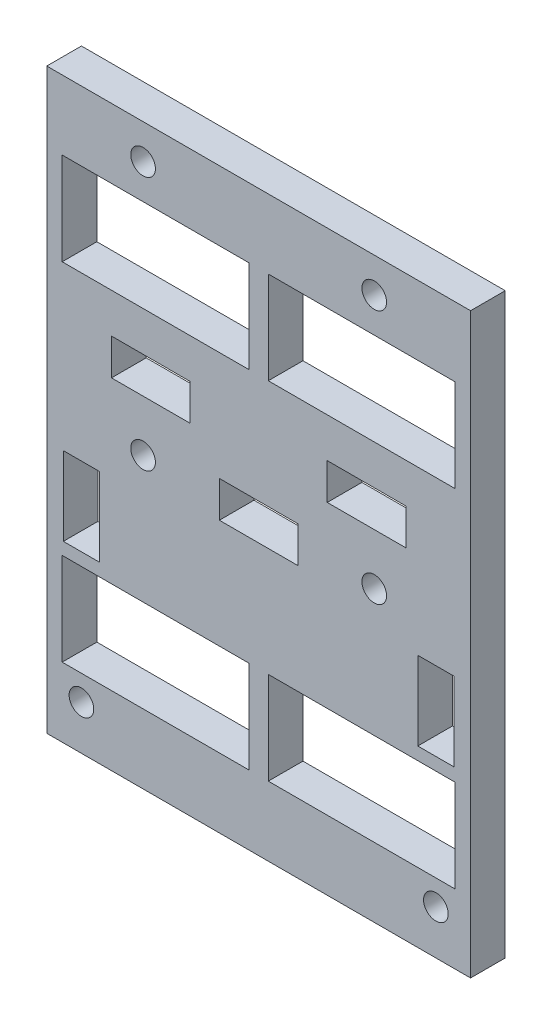
SolidWorks part; units mm, degrees
ref_plane "Front Plane" through (0, 0, 0) normal (0, 0, 1) x (1, 0, 0)
ref_plane "Top Plane" through (0, 0, 0) normal (0, 1, 0) x (1, 0, 0)
ref_plane "Right Plane" through (0, 0, 0) normal (1, 0, 0) x (0, 0, -1)
sketch "Sketch1" plane through (0, 0, 0) normal (0, 0, 1) x (1, 0, 0)
  line L0 (0, -37.5) -> (0, 37.5) construction
  line L1 (-27.5, -37.5) -> (27.5, -37.5)
  line L2 (-27.5, -37.5) -> (-27.5, 37.5)
  line L3 (-27.5, 37.5) -> (27.5, 37.5)
  line L4 (27.5, -37.5) -> (27.5, 37.5)
  line L5 (-27.5, -37.5) -> (27.5, 37.5) construction
  line L6 (-27.5, 37.5) -> (27.5, -37.5) construction
  line L7 (-27.5, 0) -> (27.5, 0) construction
  line L8 (-27.5, 22.5) -> (27.5, 22.5) construction
  line L9 (25.5, 16.5) -> (1.25, 28.5) construction
  line L10 (-25.5, 28.5) -> (-1.25, 28.5)
  line L11 (-25.5, 28.5) -> (-25.5, 16.5)
  line L12 (-25.5, 16.5) -> (-1.25, 16.5)
  line L13 (-1.25, 28.5) -> (-1.25, 16.5)
  line L14 (-25.5, 28.5) -> (-1.25, 16.5) construction
  line L15 (-25.5, 16.5) -> (-1.25, 28.5) construction
  line L16 (25.5, 28.5) -> (1.25, 16.5) construction
  line L17 (1.25, 28.5) -> (1.25, 16.5)
  line L18 (25.5, 16.5) -> (1.25, 16.5)
  line L19 (25.5, 28.5) -> (25.5, 16.5)
  line L20 (25.5, 28.5) -> (1.25, 28.5)
  line L21 (25.5, -28.5) -> (1.25, -16.5) construction
  line L22 (-25.5, -16.5) -> (-1.25, -28.5) construction
  line L23 (-25.5, -28.5) -> (-1.25, -16.5) construction
  line L24 (25.5, -16.5) -> (1.25, -28.5) construction
  line L25 (25.5, -28.5) -> (1.25, -28.5)
  line L26 (25.5, -28.5) -> (25.5, -16.5)
  line L27 (25.5, -16.5) -> (1.25, -16.5)
  line L28 (1.25, -28.5) -> (1.25, -16.5)
  line L29 (-1.25, -28.5) -> (-1.25, -16.5)
  line L30 (-25.5, -16.5) -> (-1.25, -16.5)
  line L31 (-25.5, -28.5) -> (-25.5, -16.5)
  line L32 (-25.5, -28.5) -> (-1.25, -28.5)
  point P0 (0, 0)
  point P12 (-13.375, 22.5)
  point P21 (13.375, 22.5)
  point P30 (13.375, -22.5)
  point P31 (-13.375, -22.5)
  dimension "D1" = 55
  dimension "D2" = 75
  dimension "D3" = 22.5
  dimension "D4" = 24.25
  dimension "D5" = 12
  dimension "D6" = 1.25
extrude "Boss-Extrude1" add sketch "Sketch1" along normal blind 4.5
sketch "Sketch2" plane through (0, 0, 4.5) normal (0, 0, 1) x (1, 0, 0)
  line L0 (0, -37.5) -> (0, 37.5) construction
  line L1 (-27.5, -37.5) -> (27.5, -37.5) construction
  line L2 (27.5, 37.5) -> (-27.5, 37.5) construction
  line L3 (-27.5, 0) -> (27.5, 0) construction
  line L4 (-27.5, 37.5) -> (-27.5, -37.5) construction
  line L5 (27.5, -37.5) -> (27.5, 37.5) construction
  line L6 (-15, 0) -> (15, 0) construction
  circle A0 centre (-15, 33) radius 1.6
  circle A1 centre (15, 33) radius 1.6
  circle A2 centre (15, 0) radius 1.6
  circle A3 centre (-15, 0) radius 1.6
  dimension "D1" = 3.2
  dimension "D7" = 3.2
  dimension "D8" = 3.2
  dimension "D2" = 15
  dimension "D3" = 33
  dimension "D4" = 30
  dimension "D5" = 15
  dimension "D6" = 0
extrude "screwHoles" cut sketch "Sketch2" against normal through all
sketch "Sketch3" plane through (0, 0, 4.5) normal (0, 0, 1) x (1, 0, 0)
  line L0 (-27.5, 9) -> (26.0486, 9) construction
  line L1 (-27.5, 37.5) -> (-27.5, -37.5) construction
  line L3 (0, 37.5) -> (0, -37.5) construction
  line L4 (27.5, 37.5) -> (-27.5, 37.5) construction
  line L5 (-27.5, -37.5) -> (27.5, -37.5) construction
  line L6 (19.1, 6.65) -> (8.9, 11.35) construction
  line L7 (-19.1, 11.35) -> (-8.9, 11.35)
  line L8 (-19.1, 11.35) -> (-19.1, 6.65)
  line L9 (-19.1, 6.65) -> (-8.9, 6.65)
  line L10 (-8.9, 11.35) -> (-8.9, 6.65)
  line L11 (-19.1, 11.35) -> (-8.9, 6.65) construction
  line L12 (-19.1, 6.65) -> (-8.9, 11.35) construction
  line L13 (19.1, 11.35) -> (8.9, 6.65) construction
  line L14 (8.9, 11.35) -> (8.9, 6.65)
  line L15 (19.1, 6.65) -> (8.9, 6.65)
  line L16 (19.1, 11.35) -> (19.1, 6.65)
  line L17 (19.1, 11.35) -> (8.9, 11.35)
  line L18 (-27.5, 37.5) -> (-27.5, -37.5) construction
  point P2 (-27.5, 0)
  point P12 (-14, 9)
  point P21 (14, 9)
  dimension "D1" = 10.2
  dimension "D2" = 4.7
  dimension "D3" = 14
  dimension "D4" = 9
extrude "BeltClamp" cut sketch "Sketch3" against normal through all
sketch "Sketch4" plane through (0, 0, 4.5) normal (0, 0, 1) x (1, 0, 0)
  line L0 (-27.5, 0) -> (27.5, 0) construction
  line L1 (-27.5, 37.5) -> (-27.5, -37.5) construction
  line L2 (27.5, -37.5) -> (27.5, 37.5) construction
  line L4 (-5.1, 2.35) -> (5.1, 2.35)
  line L5 (-5.1, 2.35) -> (-5.1, -2.35)
  line L6 (-5.1, -2.35) -> (5.1, -2.35)
  line L7 (5.1, 2.35) -> (5.1, -2.35)
  line L8 (-5.1, 2.35) -> (5.1, -2.35) construction
  line L9 (-5.1, -2.35) -> (5.1, 2.35) construction
  circle A0 centre (-15, 0) radius 1.6 construction
  point P6 (0, 0)
  dimension "D1" = 10.2
  dimension "D2" = 4.7
  dimension "D3" = 0
extrude "Cut-Extrude3" cut sketch "Sketch4" against normal through all
sketch "Sketch5" plane through (0, 0, 4.5) normal (0, 0, 1) x (1, 0, 0)
  line L0 (-27.5, -9.75) -> (27.5, -9.75) construction
  line L1 (-27.5, 37.5) -> (-27.5, -37.5) construction
  line L2 (27.5, -37.5) -> (27.5, 37.5) construction
  line L3 (5.1, -2.35) -> (5.1, 2.35) construction
  line L4 (0, -37.5) -> (0, 37.5) construction
  line L5 (-27.5, -37.5) -> (27.5, -37.5) construction
  line L6 (27.5, 37.5) -> (-27.5, 37.5) construction
  line L7 (-20.65, -14.85) -> (-25.35, -4.65) construction
  line L8 (20.65, -4.65) -> (25.35, -4.65)
  line L9 (20.65, -4.65) -> (20.65, -14.85)
  line L10 (20.65, -14.85) -> (25.35, -14.85)
  line L11 (25.35, -4.65) -> (25.35, -14.85)
  line L12 (20.65, -4.65) -> (25.35, -14.85) construction
  line L13 (20.65, -14.85) -> (25.35, -4.65) construction
  line L14 (-20.65, -4.65) -> (-25.35, -14.85) construction
  line L15 (-25.35, -4.65) -> (-25.35, -14.85)
  line L16 (-20.65, -14.85) -> (-25.35, -14.85)
  line L17 (-20.65, -4.65) -> (-20.65, -14.85)
  line L18 (-20.65, -4.65) -> (-25.35, -4.65)
  line L19 (23, -9.75) -> (23, -37.5) construction
  line L20 (-23, -9.75) -> (-23, -37.5) construction
  circle A0 centre (23, -31.75) radius 1.6
  circle A1 centre (-23, -31.75) radius 1.6
  point P6 (5.1, 0)
  point P15 (23, -9.75)
  point P24 (-23, -9.75)
  dimension "D5" = 3.2
  dimension "D1" = 9.75
  dimension "D2" = 10.2
  dimension "D3" = 4.7
  dimension "D4" = 23
  dimension "D6" = 22
extrude "Cut-Extrude4" cut sketch "Sketch5" against normal through all
sketch "Sketch6" plane through (0, 0, 4.5) normal (0, 0, 1) x (1, 0, 0)
  line L0 (-25.35, -9.75) -> (25.35, -9.75) construction
  line L1 (-25.35, -4.65) -> (-25.35, -14.85) construction
  line L2 (25.35, -14.85) -> (25.35, -4.65) construction
  line L3 (0, -2.35) -> (0, -37.5) construction
  line L4 (-5.1, -2.35) -> (5.1, -2.35) construction
  line L5 (-27.5, -37.5) -> (27.5, -37.5) construction
  line L6 (23, -14.85) -> (23, -4.65) construction
  line L7 (20.65, -14.85) -> (25.35, -14.85) construction
  line L8 (25.35, -4.65) -> (20.65, -4.65) construction
  line L9 (20.65, -4.65) -> (20.65, -14.85) construction
  line L10 (19.65, -15.85) -> (26.35, -15.85)
  line L11 (19.65, -15.85) -> (19.65, -3.65)
  line L12 (19.65, -3.65) -> (26.35, -3.65)
  line L13 (26.35, -15.85) -> (26.35, -3.65)
  line L14 (19.65, -15.85) -> (26.35, -3.65) construction
  line L15 (19.65, -3.65) -> (26.35, -15.85) construction
  line L16 (-19.65, -3.65) -> (-26.35, -15.85) construction
  line L17 (-19.65, -15.85) -> (-26.35, -3.65) construction
  line L18 (-23, -14.85) -> (-23, -4.65) construction
  line L19 (-26.35, -15.85) -> (-26.35, -3.65)
  line L20 (-19.65, -3.65) -> (-26.35, -3.65)
  line L21 (-19.65, -15.85) -> (-19.65, -3.65)
  line L22 (-19.65, -15.85) -> (-26.35, -15.85)
  circle A0 centre (23, -9.75) radius 1.6
  circle A1 centre (-23, -9.75) radius 1.6
  point P18 (23, -9.75)
  dimension "D3" = 3.2
  dimension "D1" = 1
  dimension "D2" = 1
extrude "FrontToRear1" [suppressed] add sketch "Sketch6" against normal up to surface (4.5 mm away) up to face at (-24.6, -31.75, 0)
sketch "Sketch7" plane through (0, 0, 4.5) normal (0, 0, 1) x (1, 0, 0)
  line L0 (5.1, 2.35) -> (-5.1, 2.35) construction
  line L1 (-20, -3.35) -> (20, -3.35)
  line L2 (-20, -3.35) -> (-20, 3.35)
  line L3 (-20, 3.35) -> (20, 3.35)
  line L4 (20, -3.35) -> (20, 3.35)
  line L5 (-20, -3.35) -> (20, 3.35) construction
  line L6 (-20, 3.35) -> (20, -3.35) construction
  circle A0 centre (15, 0) radius 1.6 construction
  point P0 (0, 0)
  dimension "D1" = 1
  dimension "D2" = 5
extrude "FrontToRear2" [suppressed] add sketch "Sketch7" against normal through all
equation "\"X-ROD-SPACING\"=45"
equation "\"Y-ROD-SPACING\"=75"
equation "\"Z-ROD-SPACING\"=17.5"
equation "\"Y-BED-OFFSET\"=2"
equation "\"Y-BED-ROD-INSET\"=3.5"
equation "\"Y-BED-SCREW-SPACING\"=209"
equation "\"Y-BED-SCREW-CUTOUT-SLOT-HEIGHT\"=1"
equation "\"T-SLOT-NUT-FILLET-RADIUS\"=0.25"
equation "\"T-SLOT-SCREW-SHAFT-RADIUS\"=1.75"
equation "\"T-SLOT-SCREW-SHAFT-CUTOUT-LENGTH\"=10.5"
equation "\"T-SLOT-NUT-DEPTH\"=4.2"
equation "\"T-SLOT-NUT-WIDTH\"=3"
equation "\"T-SLOT-NUT-END-DISTANCE\"=8"
equation "\"ACRYLIC-THICKNESS\"=10"
equation "\"ACRYLIC-THICKNESS2\"=4.5"
equation "\"ACRYLIC-TAB-CUTOUT-SIZE\"=\"ACRYLIC-THICKNESS\"+\"ACRYLIC-TAB-TOLERANCE\"*2"
equation "\"ACRYLIC-TAB-WIDTH\"=\"ACRYLIC-THICKNESS\""
equation "\"ACRYLIC-M3-HOLE\"=3.2"
equation "\"SMOOTHROD-CAP-SCREW-DISTANCE\"=20"
equation "\"FRAME-WIDTH-INNER\"=370"
equation "\"NEMA17-HOLE-SPACING\"=31"
equation "\"NEMA17-CENTRAL-CUTOUT\"=22.5"
equation "\"Z-BRACKET-REACH\"=55"
equation "\"Z-ROD-INSET\"=16"
equation "\"TOP-BRACKET-SPACING\"=40"
equation "\"SMOOTHROD-X-LENGTH\"=350"
equation "\"SMOOTHROD-Y-LENGTH\"=350"
equation "\"SMOOTHROD-Z-LENGTH\"=350"
equation "\"SMOOTHROD-TIGHTENING-HEADROOM\"=1"
equation "\"LEADSCREW-Z-LENGTH\"=300"
equation "\"SCREW-LENGTH-FRAME\"=\"ACRYLIC-THICKNESS\" + 10"
equation "\"SCREW-LENGTH-MOTOR\"=\"ACRYLIC-THICKNESS\" + 5"
equation "\"SCREW-HEAD-RADIUS\"=6"
equation "\"PRINTED-X-SMOOTHROD-DIAMETER\"=8.2"
equation "\"PRINTED-X-SMOOTHROD-CUTOUT\"=10"
equation "\"PRINTED-X-BASE-HEIGHT\"=10"
equation "\"PRINTED-LM8UU-CUTOUT-SIZE\"=16"
equation "\"PRINTED-LM8UU-CUTOUT-LENGTH\"=24.5"
equation "\"PRINTED-X-IDLER-HEIGHT\"=16"
equation "\"PSU-MOUNTING-WIDTH\"=95"
equation "\"PSU-MOUNTING-HEIGHT\"=177"
equation "\"Y-BELT-TO-ROD-DISTANCE\"=20"
equation "\"SPOOL-HOLDER-ROD-SPACING\"=150"
equation "\"D3@Sketch1\"=\"X-ROD-SPACING\"/2"
equation "\"D4@Sketch1\"=\"ACRYLIC-X-CARRIAGE-LM8UU-CUTOUT-WIDTH\""
equation "\"D1@Boss-Extrude1\"=\"ACRYLIC-THICKNESS2\""
equation "\"D1@Sketch2\"=\"ACRYLIC-M3-HOLE\""
equation "\"D1@Sketch3\"=\"ACRYLIC-TAB-CUTOUT-SIZE\""
equation "\"D2@Sketch3\"=\"ACRYLIC-THICKNESS2\"+\"ACRYLIC-TAB-TOLERANCE\"*2"
equation "\"ACRYLIC-X-CARRIAGE-WIDTH\"=55"
equation "\"ACRYLIC-X-CARRIAGE-HEIGHT\"=75"
equation "\"D1@Sketch1\"=\"ACRYLIC-X-CARRIAGE-WIDTH\""
equation "\"D2@Sketch1\"=\"ACRYLIC-X-CARRIAGE-HEIGHT\""
equation "\"ACRYLIC-X-CARRIAGE-CENTER-TAB-SPACING\"=14"
equation "\"D3@Sketch3\"=\"ACRYLIC-X-CARRIAGE-CENTER-TAB-SPACING\""
equation "\"SCREW-LENGTH-EXTRUDER\"=28"
equation "\"ACRYLIC-X-CARRIAGE-SCREW-SPACING-X\"=15"
equation "\"ACRYLIC-X-CARRIAGE-SCREW-SPACING-Y\"=33"
equation "\"D2@Sketch2\"=\"ACRYLIC-X-CARRIAGE-SCREW-SPACING-X\""
equation "\"D3@Sketch2\"=\"ACRYLIC-X-CARRIAGE-SCREW-SPACING-Y\""
equation "\"D1@Sketch4\"=\"ACRYLIC-TAB-CUTOUT-SIZE\""
equation "\"D2@Sketch4\"=\"ACRYLIC-THICKNESS2\"+\"ACRYLIC-TAB-TOLERANCE\"*2"
equation "\"D2@Sketch5\"=\"ACRYLIC-TAB-CUTOUT-SIZE\""
equation "\"D3@Sketch5\"=\"ACRYLIC-THICKNESS2\"+\"ACRYLIC-TAB-TOLERANCE\"*2"
equation "\"ACRYLIC-X-CARRIAGE-EXTRUDER-SHELF-DEPTH\"=\"ACRYLIC-X-CARRIAGE-EXTRUDER-OFFSET\" + 30"
equation "\"ACRYLIC-X-CARRIAGE-EXTRUDER-BRACE-SPACING\"=23"
equation "\"D4@Sketch5\"=\"ACRYLIC-X-CARRIAGE-EXTRUDER-BRACE-SPACING\""
equation "\"D1@Sketch5\"=\"ACRYLIC-THICKNESS2\"/2 + 7.5"
equation "\"D4@Sketch2\"=\"ACRYLIC-X-CARRIAGE-SCREW-SPACING-X\"*2"
equation "\"D5@Sketch2\"=\"ACRYLIC-X-CARRIAGE-SCREW-SPACING-X\""
equation "\"D7@Sketch2\"=\"ACRYLIC-M3-HOLE\""
equation "\"D8@Sketch2\"=\"ACRYLIC-M3-HOLE\""
equation "\"ACRYLIC-X-CARRIAGE-LM8UU-CUTOUT-WIDTH\"=24.25"
equation "\"ACRYLIC-TAB-TOLERANCE\"=.1"
equation "\"ACRYLIC-X-CARRIAGE-EXTRUDER-OFFSET\"=26"
equation "\"ACRYLIC-X-CARRIAGE-EXTRUDER-ANGLE\"=90"
equation "\"ACRYLIC-X-CARRIAGE-EXTRUDER-BRACE-TAB-OFFSET\"=20"
equation "\"ACRYLIC-X-CARRIAGE-EXTRUDER-BRACE-HEIGHT\"=35"
equation "\"ACRYLIC-X-CARRIAGE-EXTRUDER-BRACE-SCREW-SPACING\"=22"
equation "\"D5@Sketch5\"=\"ACRYLIC-M3-HOLE\""
equation "\"D3@Sketch6\"=\"ACRYLIC-M3-HOLE\""
